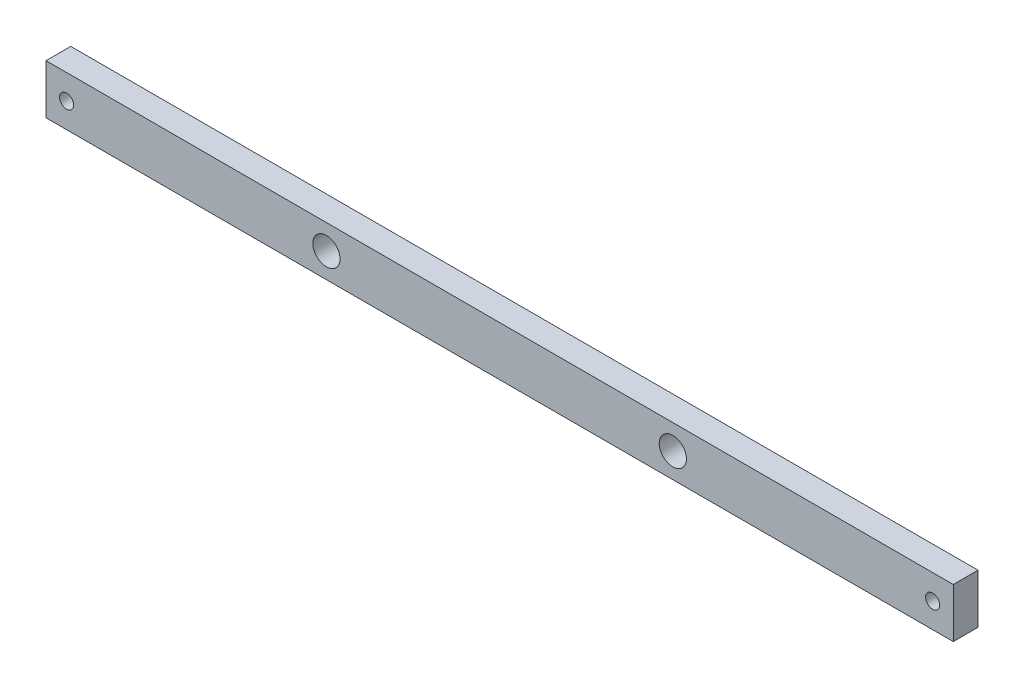
SolidWorks part; units mm, degrees
material "6061-T6 (SS)"
ref_plane "Front Plane" through (0, 0, 0) normal (0, 0, 1) x (1, 0, 0)
ref_plane "Top Plane" through (0, 0, 0) normal (0, 1, 0) x (1, 0, 0)
ref_plane "Right Plane" through (0, 0, 0) normal (1, 0, 0) x (0, 0, -1)
sketch "Sketch1" plane through (0, 0, 0) normal (0, 0, 1) x (1, 0, 0)
  line L1 (-110, -6) -> (110, -6)
  line L2 (-110, -6) -> (-110, 6)
  line L3 (-110, 6) -> (110, 6)
  line L4 (110, -6) -> (110, 6)
  circle A0 centre (-105, 0) radius 1.7
  circle A1 centre (105, 0) radius 1.7
  circle A2 centre (-42, 0) radius 3.3
  circle A3 centre (42, 0) radius 3.3
extrude "Header_Crossbeam" add sketch "Sketch1" along normal blind 6
